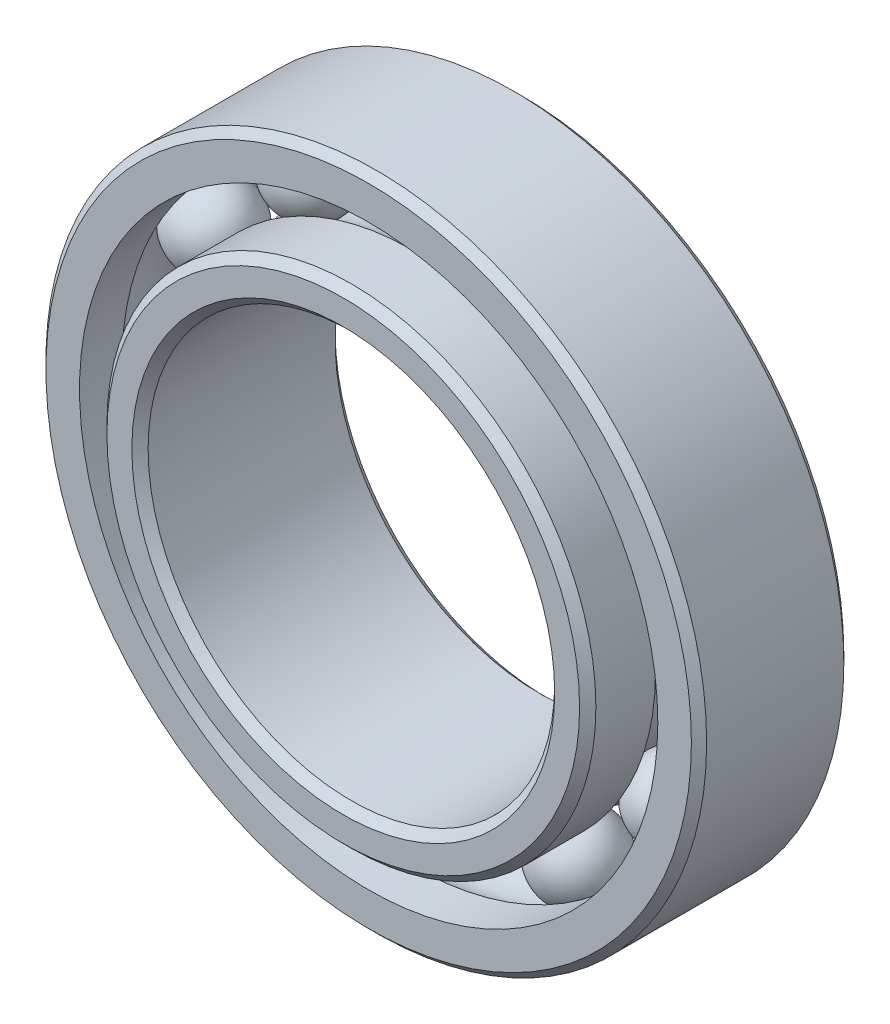
SolidWorks part; units mm, degrees
ref_plane "Front Plane" through (0, 0, 0) normal (0, 0, 1) x (1, 0, 0)
ref_plane "Top Plane" through (0, 0, 0) normal (0, 1, 0) x (1, 0, 0)
ref_plane "Right Plane" through (0, 0, 0) normal (1, 0, 0) x (0, 0, -1)
sketch "Sketch1" plane through (0, 0, 0) normal (1, 0, 0) x (0, 0, -1)
  line L0 (-4.7625, 0) -> (4.7625, 0) construction
  line L1 (0, 20.6375) -> (0, -20.6375) construction
  line L2 (4.2863, 20.6375) -> (-4.2863, 20.6375)
  line L3 (-4.2863, 20.6375) -> (-4.7625, 20.1612)
  line L4 (-4.7625, 20.1612) -> (-4.7625, 18.0644)
  line L5 (-4.7625, 18.0644) -> (-2.1167, 18.0644)
  line L6 (4.7625, 18.0644) -> (2.1167, 18.0644)
  line L7 (4.7625, 20.1612) -> (4.7625, 18.0644)
  line L8 (4.2863, 20.6375) -> (4.7625, 20.1612)
  line L9 (0, 20.6375) -> (0, 16.6687) construction
  line L10 (0, 16.6687) -> (0, 12.7) construction
  arc A0 (-2.1167, 18.0644) -> (2.1167, 18.0644) centre (0, 16.6687) cw
  point P14 (0, 12.7)
  dimension "D3" = 4.2333
  dimension "D1" = 45
  dimension "Width" = 9.525
  dimension "OD" = 41.275
  dimension "D2" = 0.4763
  dimension "Shaft Dia" = 25.4
  dimension "D4" = 1.3956
revolve "Revolve1" add sketch "Sketch1" angle 360 about L0
sketch "Sketch3" plane through (0, 0, 0) normal (1, 0, 0) x (0, 0, -1)
  line L0 (-6.35, 15.2731) -> (-2.1167, 15.2731)
  line L1 (0, 20.6375) -> (0, -20.6375) construction
  line L3 (0, 16.6687) -> (0, 12.7) construction
  line L4 (6.35, 15.2731) -> (6.35, 12.7)
  line L5 (-6.35, 15.2731) -> (-6.35, 12.7)
  line L6 (-6.35, 12.7) -> (6.35, 12.7)
  line L11 (6.35, 15.2731) -> (2.1167, 15.2731)
  arc A0 (2.1167, 18.0644) -> (-2.1167, 18.0644) centre (0, 16.6687) ccw construction
  arc A1 (2.1167, 15.2731) -> (-2.1167, 15.2731) centre (0, 16.6687) cw
  dimension "D1" = 12.7
revolve "Revolve3" add sketch "Sketch3" angle 360 about L0
sketch "Sketch4" plane through (0, 0, 0) normal (1, 0, 0) x (0, 0, -1)
  line L0 (-2.5353, 16.6687) -> (2.5353, 16.6687)
  arc A2 (-2.5353, 16.6687) -> (2.5353, 16.6687) centre (0, 16.6687) cw
  arc A3 (2.1167, 18.0644) -> (-2.1167, 18.0644) centre (0, 16.6687) ccw construction
revolve "Revolve4" add sketch "Sketch4" angle 360 about L0
ref_axis "Axis1" through (0, 0, -4.7625) along (0, 0, 1)
pattern_circular "CirPattern1" count 12 every 30 about axis through (0, 0, -4.7625) along (0, 0, 1) of bodies 104
chamfer "Chamfer1" distance 0.508 angle 45 4 edges at (12.7, 0, 6.35) (15.2731, 0, 6.35) (15.2731, 0, -6.35) (12.7, 0, -6.35)
equation "\"D2@Sketch1\" = \"Width@Sketch1\"*.05"
equation "\"D3@Sketch1\" = \"Width@Sketch1\"/2.25"
equation "\"D4@Sketch1\" = (((\"OD@Sketch1\"-\"Width@Sketch1\")/2)/3.25)/3.5"
equation "\"D2@CirPattern1\" = 360/\"Balls@CirPattern1\""
